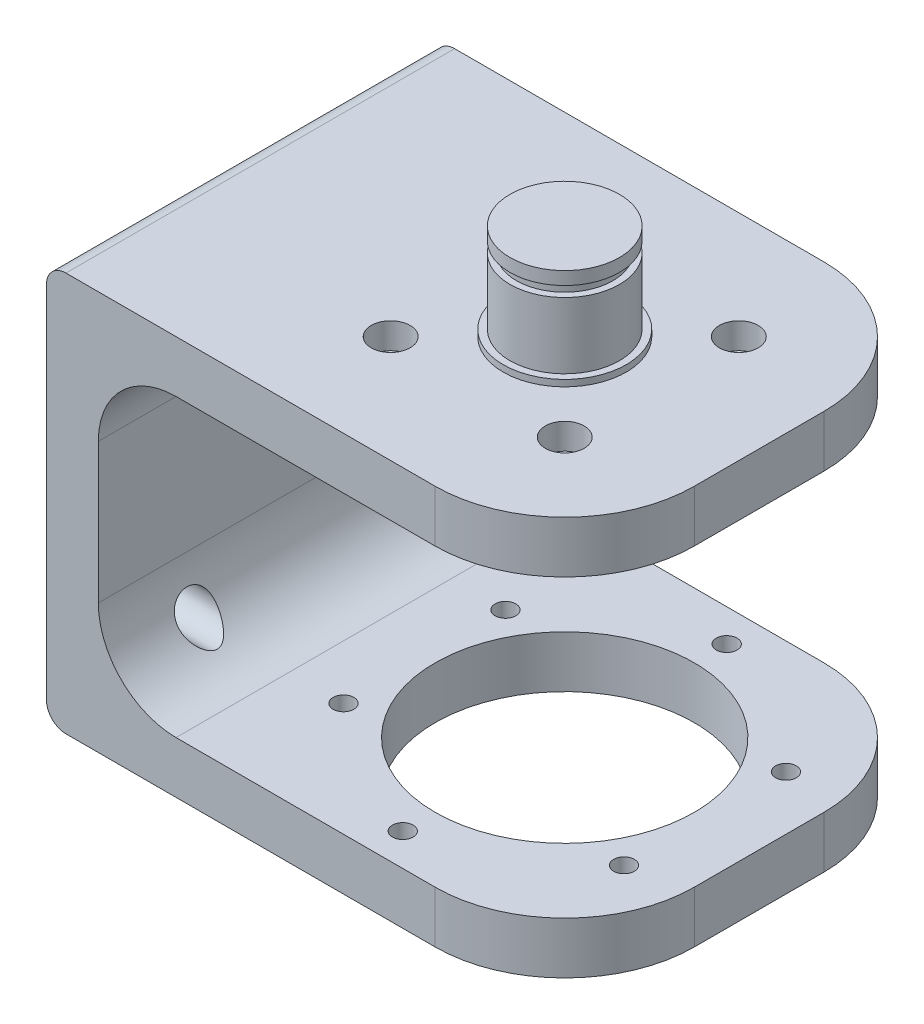
SolidWorks part; units mm, degrees
material "PETG-CF"
ref_plane "Front Plane" through (0, 0, 0) normal (0, 0, 1) x (1, 0, 0)
ref_plane "Top Plane" through (0, 0, 0) normal (0, 1, 0) x (1, 0, 0)
ref_plane "Right Plane" through (0, 0, 0) normal (1, 0, 0) x (0, 0, -1)
sketch "草图1" plane through (0, 0, 0) normal (0, 1, 0) x (1, 0, 0)
  line L1 (40, -30) -> (-40, -30)
  line L2 (40, -30) -> (40, 30)
  line L3 (40, 30) -> (-40, 30)
  line L4 (-40, -30) -> (-40, 30)
  line L5 (40, -30) -> (-40, 30) construction
  line L6 (40, 30) -> (-40, -30) construction
  point P0 (0, 0)
  dimension "D1" = 60
  dimension "D2" = 80
extrude "凸台-拉伸1" add sketch "草图1" along normal blind 8
sketch "草图2" plane through (0, 8, 0) normal (0, 1, 0) x (1, 0, 0)
  line L1 (-32, -30) -> (-40, -30)
  line L2 (-32, -30) -> (-32, 30)
  line L3 (-32, 30) -> (-40, 30)
  line L4 (-40, -30) -> (-40, 30)
  line L5 (-32, -30) -> (-40, 30) construction
  line L6 (-32, 30) -> (-40, -30) construction
  point P0 (-36, 0)
  dimension "D1" = 8
extrude "凸台-拉伸2" add sketch "草图2" along normal blind 53.6
sketch "草图5" plane through (-32, 0, 0) normal (1, 0, 0) x (0, 0, -1)
  line L0 (-30, 61.6) -> (-30, 8) construction
  line L1 (30, 53.6) -> (-30, 53.6)
  line L2 (30, 53.6) -> (30, 61.6)
  line L3 (30, 61.6) -> (-30, 61.6)
  line L4 (-30, 53.6) -> (-30, 61.6)
  line L5 (30, 53.6) -> (-30, 61.6) construction
  line L6 (30, 61.6) -> (-30, 53.6) construction
  line L7 (30, 61.6) -> (30, 8) construction
  line L9 (-30, 61.6) -> (30, 61.6) construction
  point P0 (0, 57.6)
  dimension "D1" = 8
extrude "凸台-拉伸3" add sketch "草图5" along normal through all
sketch "草图4" plane through (0, 8, 0) normal (0, 1, 0) x (1, 0, 0)
  line L2 (40, -30) -> (40, 30) construction
  line L3 (40, 30) -> (-32, 30) construction
  circle A0 centre (10, 0) radius 25 construction
  circle A1 centre (10, 25) radius 1.6
  circle A2 centre (-11.6506, 12.5) radius 1.6
  circle A3 centre (-11.6506, -12.5) radius 1.6
  circle A4 centre (10, -25) radius 1.6
  circle A5 centre (10, 0) radius 20
  circle A6 centre (31.6506, -12.5) radius 1.6
  circle A7 centre (31.6506, 12.5) radius 1.6
  point P17 (10, 0)
  dimension "D3" = 50
  dimension "D4" = 3.2
  dimension "D6" = 40
  dimension "D1" = 30
  dimension "D2" = 30
  dimension "D5" = 6
extrude "切除-拉伸1" cut sketch "草图4" against normal through all contours A5 | A2 | A1 | A4 | A3 | A7 | A6
sketch "草图7" plane through (0, 61.6, 0) normal (0, 1, 0) x (1, 0, 0)
  line L1 (40, 30) -> (-40, 30) construction
  line L2 (40, 30) -> (40, -30) construction
  line L3 (10, 0) -> (-3.435, 13.435) construction
  line L4 (10, 0) -> (10, 19) construction
  circle A0 centre (10, 0) radius 19 construction
  circle A5 centre (-3.435, 13.435) radius 1.6
  circle A6 centre (23.435, 13.435) radius 1.6
  circle A7 centre (23.435, -13.435) radius 1.6
  circle A8 centre (-3.435, -13.435) radius 1.6
  point P18 (10, 0)
  point P20 (10, 0)
  dimension "D1" = 38
  dimension "D4" = 45
  dimension "D5" = 3.2
  dimension "D2" = 30
  dimension "D3" = 30
  dimension "D6" = 4
extrude "切除-拉伸3" cut sketch "草图7" against normal up to next
fillet "圆角3" radius 20 4 edges at (40, 4, 30) (40, 4, -30) (40, 57.6, -30) (40, 57.6, 30)
fillet "圆角4" radius 12 2 edges at (-32, 8, 0) (-32, 53.6, 0)
fillet "圆角5" radius 3 2 edges at (-40, 0, 0) (-40, 61.6, 0)
sketch "草图6" plane through (-40, 0, 0) normal (-1, 0, 0) x (0, 0, 1)
  line L0 (-30, 61.6) -> (30, 61.6) construction
  line L1 (17, 13) -> (-17, 13) construction
  line L2 (17, 13) -> (17, 48.6) construction
  line L3 (17, 48.6) -> (-17, 48.6) construction
  line L4 (-17, 13) -> (-17, 48.6) construction
  line L5 (17, 13) -> (-17, 48.6) construction
  line L6 (17, 48.6) -> (-17, 13) construction
  line L7 (30, 0) -> (-30, 0) construction
  line L8 (30, 58.6) -> (30, 3) construction
  line L9 (-30, 58.6) -> (-30, 3) construction
  line L10 (-17, 30.8) -> (17, 30.8) construction
  line L11 (0, 13) -> (0, 48.6) construction
  circle A0 centre (-17, 48.6) radius 1.6
  circle A1 centre (17, 48.6) radius 1.6
  circle A2 centre (17, 13) radius 1.6
  circle A3 centre (-17, 13) radius 1.6
  point P0 (0, 30.8)
  dimension "D5" = 3.2
  dimension "D1" = 13
  dimension "D2" = 13
  dimension "D3" = 13
  dimension "D4" = 13
extrude "切除-拉伸2" cut sketch "草图6" against normal through all
sketch "草图8" plane through (0, 61.6, 0) normal (0, 1, 0) x (1, 0, 0)
  circle A0 centre (10, 0) radius 8.45
  dimension "D1" = 16.9
extrude "凸台-拉伸4" add sketch "草图8" along normal blind 14.8
ref_plane "基准面1" through (0, 74.4, 0) normal (0, 1, 0) x (1, 0, 0)
sketch "草图10" plane through (0, 74.4, 0) normal (0, 1, 0) x (1, 0, 0)
  circle A0 centre (10, 0) radius 8.45
  circle A1 centre (10, 0) radius 7.45
  dimension "D1" = 14.9
extrude "切除-拉伸4" cut sketch "草图10" against normal blind 1.6
ref_plane "基准面2" through (-36, 0, 0) normal (-1, 0, 0) x (0, 0, 1)
sketch "草图12" plane through (-36, 0, 0) normal (-1, 0, 0) x (0, 0, 1)
  line L0 (-30, 30.8) -> (30, 30.8) construction
  line L1 (-30, 58.6) -> (-30, 3) construction
  line L2 (30, 58.6) -> (30, 3) construction
  line L3 (0, 61.6) -> (0, 3) construction
  line L4 (8.45, 61.6) -> (-8.45, 61.6) construction
  line L5 (-30, 3) -> (30, 3) construction
  circle A0 centre (-17, 48.6) radius 3
  circle A1 centre (17, 48.6) radius 3
  circle A2 centre (17, 13) radius 3
  circle A3 centre (-17, 13) radius 3
  dimension "D1" = 6
extrude "切除-拉伸5" cut sketch "草图12" against normal up to next
sketch "草图14" plane through (0, 61.6, 0) normal (0, 1, 0) x (1, 0, 0)
  circle A0 centre (-3.435, 13.435) radius 3
  circle A1 centre (23.435, 13.435) radius 3
  circle A2 centre (23.435, -13.435) radius 3
  circle A3 centre (-3.435, -13.435) radius 3
  point P12 (10, 0)
  dimension "D1" = 6
  dimension "D2" = 4
extrude "切除-拉伸6" cut sketch "草图14" against normal blind 4
sketch "草图15" plane through (0, 0, 0) normal (0, -1, 0) x (1, 0, 0)
  circle A0 centre (-11.6506, 12.5) radius 3
  circle A1 centre (10, 25) radius 3
  circle A2 centre (31.6506, 12.5) radius 3
  circle A3 centre (31.6506, -12.5) radius 3
  circle A4 centre (10, -25) radius 3
  circle A5 centre (-11.6506, -12.5) radius 3
  point P15 (10, 0)
  dimension "D1" = 6
  dimension "D2" = 6
extrude "切除-拉伸7" cut sketch "草图15" against normal blind 4
sketch "草图16" plane through (0, 61.6, 0) normal (0, 1, 0) x (1, 0, 0)
  circle A0 centre (10, 0) radius 9.5
  dimension "D1" = 19
extrude "凸台-拉伸5" add sketch "草图16" along normal blind 1
